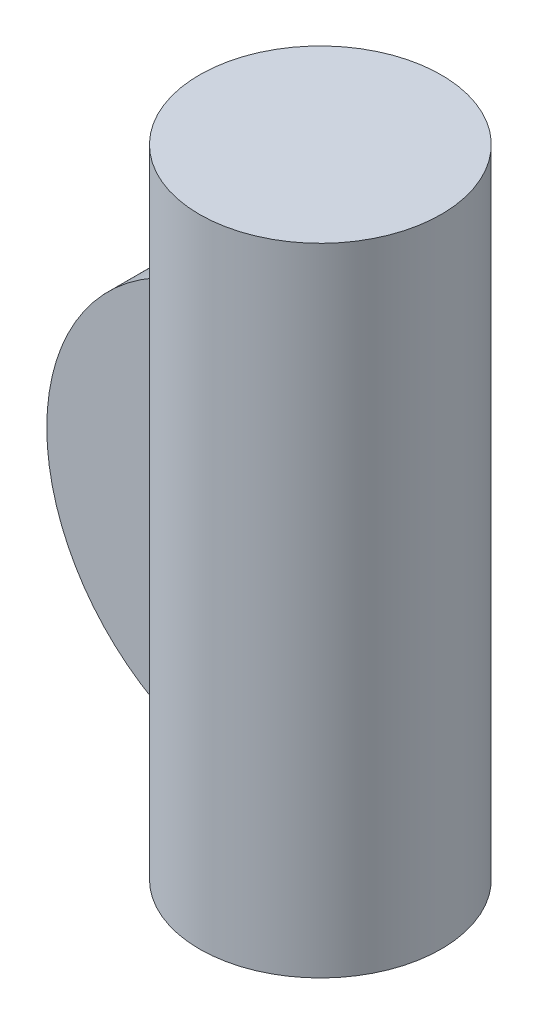
SolidWorks part; units mm, degrees
ref_plane "Front Plane" through (0, 0, 0) normal (0, 0, 1) x (1, 0, 0)
ref_plane "Top Plane" through (0, 0, 0) normal (0, 1, 0) x (1, 0, 0)
ref_plane "Right Plane" through (0, 0, 0) normal (1, 0, 0) x (0, 0, -1)
sketch "Sketch1" plane through (0, 0, 0) normal (0, 1, 0) x (1, 0, 0)
  circle A0 centre (0, 0) radius 2.413
  dimension "D1" = 4.826
extrude "Boss-Extrude1" add sketch "Sketch1" along normal blind 12.7
sketch "Sketch2" plane through (0, 0, 0) normal (0, 0, 1) x (1, 0, 0)
  line L0 (2.413, 12.7) -> (-2.413, 12.7) construction
  line L1 (0, 0) -> (0, 10.541)
  circle A0 centre (0, 6.35) radius 4.191
  dimension "D1" = 8.382
  dimension "D2" = 6.35
extrude "Boss-Extrude2" add sketch "Sketch2" along normal blind 1.27 and the other way blind 1.27 contours L1 A0 region at (-1.7787, 6.35, 0)
